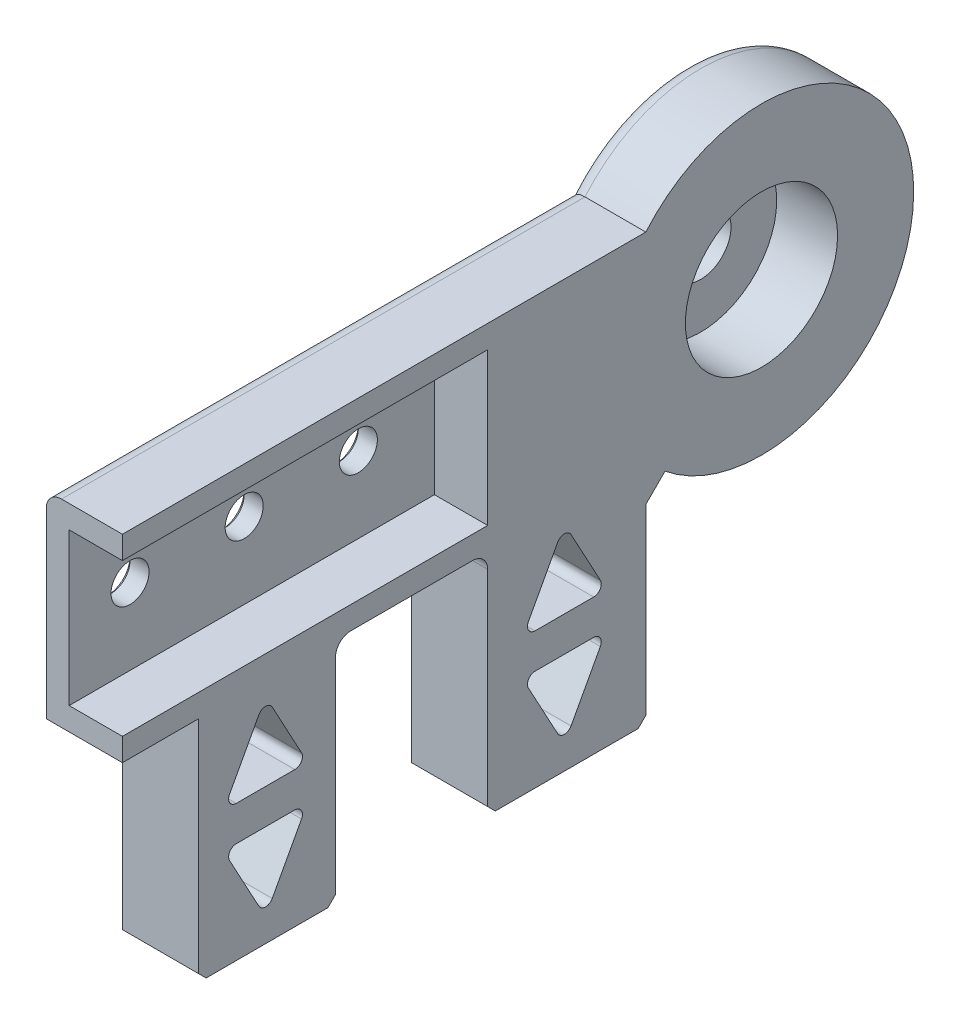
SolidWorks part; units mm, degrees
ref_plane "前视基准面" through (0, 0, 0) normal (0, 0, 1) x (1, 0, 0)
ref_plane "上视基准面" through (0, 0, 0) normal (0, 1, 0) x (1, 0, 0)
ref_plane "右视基准面" through (0, 0, 0) normal (1, 0, 0) x (0, 0, -1)
sketch "草图1" plane through (0, 0, 0) normal (1, 0, 0) x (0, 0, -1)
  line L1 (-31.9868, 13) -> (31.9868, 13)
  line L2 (-31.9868, 13) -> (-31.9868, -13)
  line L3 (-31.9868, -13) -> (31.9868, -13)
  line L4 (31.9868, 13) -> (31.9868, -13)
  line L5 (-31.9868, 13) -> (31.9868, -13) construction
  line L6 (-31.9868, -13) -> (31.9868, 13) construction
  circle A0 centre (31.9868, 0) radius 20
  point P0 (0, 0)
  dimension "D2" = 40
  dimension "D1" = 26
extrude "凸台-拉伸1" add sketch "草图1" along normal blind 10 contours L3 A0 L1 L4 | L1 L4 L3 L2 region at (0, 0, -37.7439)
sketch "草图2" plane through (10, 0, 0) normal (1, 0, 0) x (0, 0, -1)
  line L0 (-31.9868, 13) -> (-31.9868, -13) construction
  line L1 (-31.9868, 10) -> (13.0132, 10)
  line L2 (-31.9868, 10) -> (-31.9868, -10)
  line L3 (-31.9868, -10) -> (13.0132, -10)
  line L4 (13.0132, 10) -> (13.0132, -10)
  line L5 (-31.9868, 13) -> (16.7881, 13) construction
  line L6 (-31.9868, -13) -> (16.7881, -13) construction
  dimension "D1" = 3
  dimension "D2" = 3
  dimension "D3" = 45
extrude "切除-拉伸1" cut sketch "草图2" against normal blind 7
sketch "草图3" plane through (10, 0, 0) normal (1, 0, 0) x (0, 0, -1)
  circle A0 centre (31.9868, 0) radius 10
  dimension "D1" = 20
extrude "切除-拉伸2" cut sketch "草图3" against normal blind 8
sketch "草图4" plane through (2, 0, 0) normal (1, 0, 0) x (0, 0, -1)
  circle A0 centre (31.9868, 0) radius 4
  dimension "D1" = 8
extrude "切除-拉伸3" cut sketch "草图4" against normal blind 7
sketch "草图6" plane through (0, -13, 0) normal (0, -1, 0) x (1, 0, 0)
  line L0 (10, 31.9868) -> (10, -16.7881) construction
  line L1 (0, -16.7881) -> (10, -16.7881)
  line L2 (0, -16.7881) -> (0, -8.7881)
  line L3 (0, -8.7881) -> (10, -8.7881)
  line L4 (10, -16.7881) -> (10, -8.7881)
  line L6 (0, 31.9868) -> (10, 31.9868)
  line L7 (0, 31.9868) -> (0, 23.9868)
  line L8 (0, 23.9868) -> (10, 23.9868)
  line L9 (10, 31.9868) -> (10, 23.9868)
  dimension "D1" = 8
  dimension "D2" = 8
extrude "凸台-拉伸2" add sketch "草图6" along normal blind 15
chamfer "倒角2" distance 5 angle 45 1 edges at (5, -13, -16.7881) first distance on face at (5, -20.5, -16.7881)
sketch "草图7" plane through (0, 0, 31.9868) normal (0, 0, 1) x (1, 0, 0)
  line L8 (3, -10) -> (3, 10)
  line L9 (3, 10) -> (10, 10)
  line L10 (10, 10) -> (10, 13)
  line L11 (10, 13) -> (0, 13)
  line L12 (0, 13) -> (0, -28)
  line L13 (0, -28) -> (10, -28)
  line L14 (10, -28) -> (10, -10)
  line L15 (10, -10) -> (3, -10)
  line L16 (3, -10) -> (3, 10)
  line L17 (3, 10) -> (10, 10)
  line L18 (10, 10) -> (10, 13)
  line L19 (10, 13) -> (0, 13)
  line L20 (0, 13) -> (0, -28)
  line L21 (0, -28) -> (10, -28)
  line L22 (10, -28) -> (10, -10)
  line L23 (10, -10) -> (3, -10)
  dimension "D1" = 0
extrude "凸台-拉伸3" add sketch "草图7" along normal blind 20
sketch "草图8" plane through (0, -13, 0) normal (0, -1, 0) x (1, 0, 0)
  line L0 (10, 23.9868) -> (10, -8.7881) construction
  line L1 (0, -8.7881) -> (10, -8.7881)
  line L2 (0, -8.7881) -> (0, 3.9868)
  line L3 (0, 3.9868) -> (10, 3.9868)
  line L4 (10, -8.7881) -> (10, 3.9868)
  line L5 (0, 23.9868) -> (10, 23.9868) construction
  dimension "D1" = 20
extrude "凸台-拉伸4" add sketch "草图8" along normal up to surface (15 mm away) up to face at (5, -28, -12.7881)
sketch "草图9" plane through (0, 0, -13.0132) normal (0, 0, 1) x (1, 0, 0)
  line L4 (10, -10) -> (10, 10)
  line L5 (10, 10) -> (3, 10)
  line L6 (3, 10) -> (3, -10)
  line L7 (3, -10) -> (10, -10)
  line L8 (10, -10) -> (10, 10)
  line L9 (10, 10) -> (3, 10)
  line L10 (3, 10) -> (3, -10)
  line L11 (3, -10) -> (10, -10)
  dimension "D1" = 0
extrude "凸台-拉伸5" add sketch "草图9" along normal blind 10
sketch "草图10" plane through (0, 0, -3.0132) normal (0, 0, 1) x (1, 0, 0)
  line L4 (3, -10) -> (10, -10)
  line L5 (10, -10) -> (10, 10)
  line L6 (10, 10) -> (3, 10)
  line L7 (3, 10) -> (3, -10)
  line L8 (3, -10) -> (10, -10)
  line L9 (10, -10) -> (10, 10)
  line L10 (10, 10) -> (3, 10)
  line L11 (3, 10) -> (3, -10)
  dimension "D1" = 0
extrude "凸台-拉伸6" add sketch "草图10" along normal blind 7
sketch "草图11" plane through (10, 0, 0) normal (1, 0, 0) x (0, 0, -1)
  line L0 (-51.9868, -28) -> (-51.9868, -10) construction
  line L1 (-51.9868, -13) -> (-41.9868, -13)
  line L2 (-51.9868, -13) -> (-51.9868, -28)
  line L3 (-51.9868, -28) -> (-41.9868, -28)
  line L4 (-41.9868, -13) -> (-41.9868, -28)
  line L5 (-23.9868, -28) -> (-51.9868, -28) construction
  dimension "D1" = 10
extrude "切除-拉伸5" cut sketch "草图11" against normal through all
sketch "草图12" plane through (0, -28, 0) normal (0, -1, 0) x (1, 0, 0)
  line L4 (10, 41.9868) -> (0, 41.9868)
  line L5 (0, 41.9868) -> (0, 23.9868)
  line L6 (0, 23.9868) -> (10, 23.9868)
  line L7 (10, 23.9868) -> (10, 41.9868)
  line L8 (10, 41.9868) -> (0, 41.9868)
  line L9 (0, 41.9868) -> (0, 23.9868)
  line L10 (0, 23.9868) -> (10, 23.9868)
  line L11 (10, 23.9868) -> (10, 41.9868)
  line L12 (0, 3.9868) -> (0, -16.7881)
  line L13 (0, -16.7881) -> (10, -16.7881)
  line L14 (10, -16.7881) -> (10, 3.9868)
  line L15 (10, 3.9868) -> (0, 3.9868)
  line L16 (0, 3.9868) -> (0, -16.7881)
  line L17 (0, -16.7881) -> (10, -16.7881)
  line L18 (10, -16.7881) -> (10, 3.9868)
  line L19 (10, 3.9868) -> (0, 3.9868)
  dimension "D1" = 0
  dimension "D2" = 0
extrude "凸台-拉伸7" add sketch "草图12" along normal blind 15
sketch "草图13" plane through (0, 0, 0) normal (-1, 0, 0) x (0, 0, 1)
  line L0 (-11.6113, -29.6978) -> (-0.5588, -29.6978)
  line L1 (-0.5588, -29.6978) -> (-6.0851, -39.9161)
  line L2 (-6.0851, -39.9161) -> (-11.6113, -29.6978)
  line L3 (-16.7881, -27.4016) -> (41.9868, -27.4016) construction
  line L4 (-6.0851, -14.887) -> (-11.6113, -25.1053)
  line L5 (-0.5588, -25.1053) -> (-6.0851, -14.887)
  line L6 (-11.6113, -25.1053) -> (-0.5588, -25.1053)
  line L7 (-16.7881, -43) -> (-16.7881, -18) construction
  line L8 (41.9868, -43) -> (41.9868, -13) construction
  line L9 (13.5479, -10.1797) -> (13.5479, -39.9161) construction
  line L10 (38.7071, -25.1053) -> (27.6546, -25.1053)
  line L11 (27.6546, -25.1053) -> (33.1809, -14.887)
  line L12 (33.1809, -14.887) -> (38.7071, -25.1053)
  line L13 (33.1809, -39.9161) -> (38.7071, -29.6978)
  line L14 (27.6546, -29.6978) -> (33.1809, -39.9161)
  line L15 (38.7071, -29.6978) -> (27.6546, -29.6978)
extrude "切除-拉伸6" cut sketch "草图13" against normal blind 15
fillet "圆角1" radius 1 12 edges at (5, -29.6978, 38.7071) (5, -29.6978, 27.6546) (5, -39.9161, 33.1809) (5, -25.1053, 38.7071) (5, -14.887, 33.1809) (5, -25.1053, 27.6546) (5, -39.9161, -6.0851) (5, -29.6978, -0.5588) (5, -29.6978, -11.6113) (5, -25.1053, -0.5588) (5, -14.887, -6.0851) (5, -25.1053, -11.6113)
chamfer "倒角3" distance 1 angle 45 4 edges at (5, -43, 41.9868) (5, -43, -16.7881) (5, -43, 23.9868) (5, -43, 3.9868)
fillet "圆角2" radius 2 2 edges at (5, -13, 3.9868) (5, -13, 23.9868)
sketch "草图14" plane through (0, 0, 0) normal (-1, 0, 0) x (0, 0, 1)
  circle A0 centre (-31.9868, 0) radius 7.5
  circle A1 centre (-31.9868, 0) radius 4
  dimension "D1" = 15
extrude "凸台-拉伸8" add sketch "草图14" along normal blind 2
fillet "圆角3" radius 2 1 edges at (-2, 0, -24.4868)
sketch "草图16" plane through (3, 0, 0) normal (1, 0, 0) x (0, 0, -1)
  line L0 (0, 0) -> (-57.7508, 0) construction
  line L1 (-51.9868, -10) -> (-51.9868, 10) construction
  circle A0 centre (-43.9868, 0) radius 2.5
  circle A1 centre (-28.9868, 0) radius 2.5
  circle A2 centre (-13.9868, 0) radius 2.5
  dimension "D1" = 5
  dimension "D2" = 8
  dimension "D3" = 3
extrude "切除-拉伸7" cut sketch "草图16" against normal blind 3
chamfer "倒角4" distance 0.5 angle 45 3 edges at (0, 0, 41.4868) (0, 0, 26.4868) (0, 0, 11.4868)
fillet "圆角4" radius 2 2 edges at (0, 13, 17.5993) (0, 1.7679, -51.9085)
